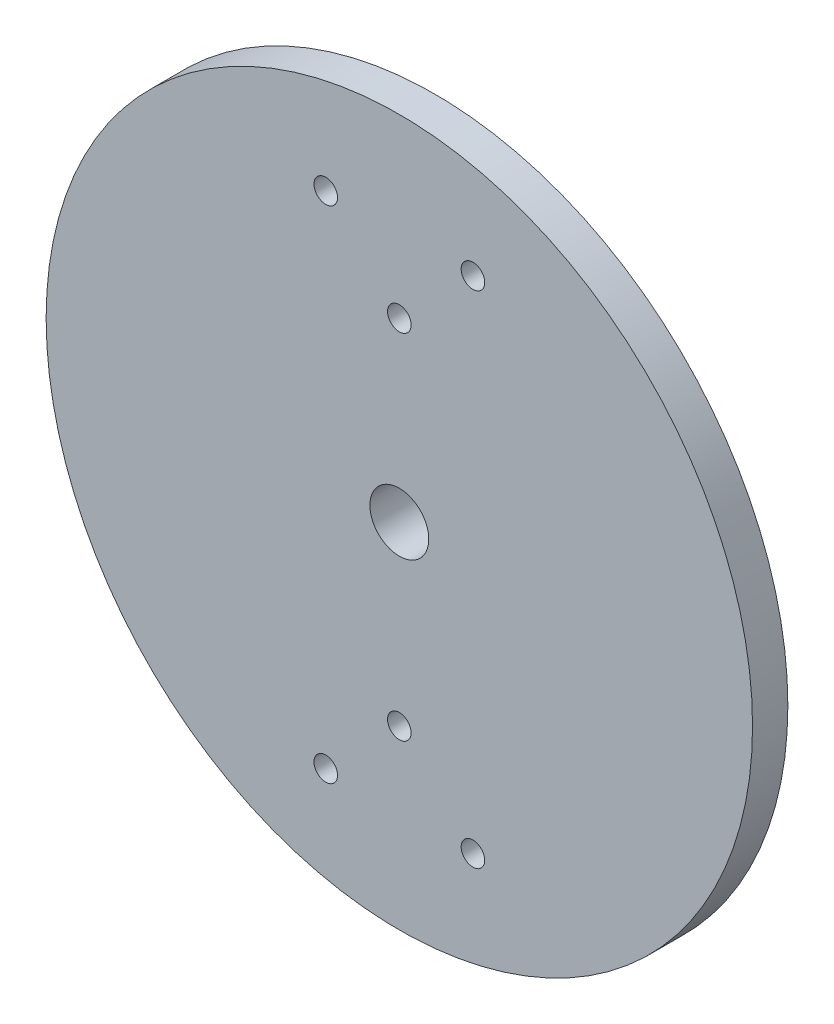
SolidWorks part; units mm, degrees
material "Oak"
ref_plane "Front Plane" through (0, 0, 0) normal (0, 0, 1) x (1, 0, 0)
ref_plane "Top Plane" through (0, 0, 0) normal (0, 1, 0) x (1, 0, 0)
ref_plane "Right Plane" through (0, 0, 0) normal (1, 0, 0) x (0, 0, -1)
sketch "Sketch1" plane through (0, 0, 0) normal (0, 0, 1) x (1, 0, 0)
  line L8 (-139.7, 139.7) -> (-139.7, -139.7)
  line L9 (-139.7, -139.7) -> (139.7, -139.7)
  line L10 (139.7, -139.7) -> (139.7, 139.7)
  line L11 (139.7, 139.7) -> (-139.7, 139.7)
  circle A1 centre (0, 0) radius 38.1
  circle A5 centre (0, 0) radius 38.1
  circle A6 centre (0, 0) radius 6.35
  circle A7 centre (0, 0) radius 12.7
  circle A8 centre (0, 0) radius 76.2
  dimension "D2" = 152.4
extrude "Boss-Extrude1" add sketch "Sketch1" along normal blind 7.62 contours A8 A1 | A1 A7 | A7 A6 region at (-37.0224, 0, 0) region at (-12.3408, 0, 0) region at (-74.0447, 0, 0)
sketch "Sketch2" plane through (0, 0, 0) normal (0, 0, -1) x (-1, 0, 0)
  circle A0 centre (0, 0) radius 35.56
  circle A1 centre (0, 0) radius 76.2
  circle A2 centre (0, 0) radius 76.2
  dimension "D2" = 71.12
  dimension "D1" = 0
extrude "Boss-Extrude2" add sketch "Sketch2" along normal blind 5.08 contours A0
sketch "Sketch3" plane through (0, 0, 7.62) normal (0, 0, 1) x (1, 0, 0)
  line L0 (0, 76.2) -> (0, -76.2) construction
  line L1 (6.35, 0) -> (88.5796, 0) construction
  line L2 (-9.525, 63.5) -> (9.525, 63.5)
  line L3 (-9.525, 63.5) -> (-9.525, 44.45)
  line L4 (-9.525, 44.45) -> (9.525, 44.45)
  line L5 (9.525, 63.5) -> (9.525, 44.45)
  line L6 (-9.525, -44.45) -> (9.525, -44.45)
  line L7 (-9.525, -44.45) -> (-9.525, -63.5)
  line L8 (-9.525, -63.5) -> (9.525, -63.5)
  line L9 (9.525, -44.45) -> (9.525, -63.5)
  circle A0 centre (0, 0) radius 76.2 construction
  circle A1 centre (15.875, -53.975) radius 2.54
  circle A2 centre (-15.875, -53.975) radius 2.54
  circle A3 centre (0, -38.1) radius 2.54
  circle A7 centre (0, 0) radius 6.35 construction
  circle A8 centre (-15.875, 53.975) radius 2.54
  circle A9 centre (0, 38.1) radius 2.54
  circle A10 centre (15.875, 53.975) radius 2.54
  circle M15 centre (0, 0) radius 6.35
  dimension "D9" = 5.08
  dimension "D10" = 5.08
  dimension "D11" = 5.08
  dimension "D1" = 12.7
  dimension "D2" = 12.7
  dimension "D3" = 19.05
  dimension "D4" = 19.05
  dimension "D5" = 9.525
  dimension "D6" = 19.05
  dimension "D7" = 19.05
  dimension "D8" = 9.525
  dimension "D15" = 6.35
  dimension "D16" = 6.35
  dimension "D17" = 15.875
  dimension "D18" = 9.525
  dimension "D19" = 9.525
extrude "Cut-Extrude2" cut sketch "Sketch3" against normal blind 25.4 contours A2 | A1 | A10 | A9 | A8 | M15 | A3 region at (15.875, -53.975, 7.62) region at (-15.875, -53.975, 7.62) region at (-15.875, 53.975, 7.62) region at (0, 38.1, 7.62) region at (15.875, 53.975, 7.62) region at (0, 0, 7.62)
